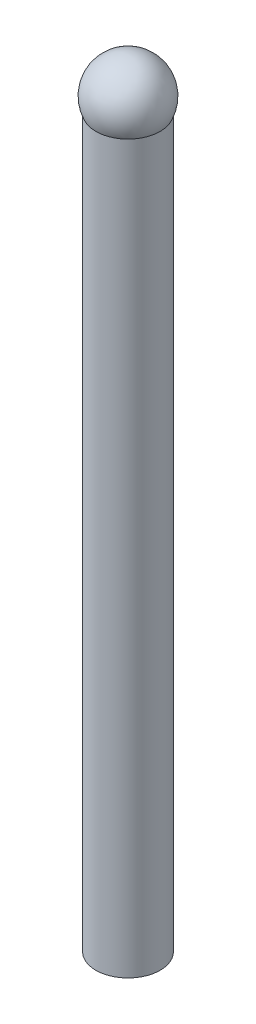
SolidWorks part; units mm, degrees
ref_plane "Спереди" through (0, 0, 0) normal (0, 0, 1) x (1, 0, 0)
ref_plane "Сверху" through (0, 0, 0) normal (0, 1, 0) x (1, 0, 0)
ref_plane "Справа" through (0, 0, 0) normal (1, 0, 0) x (0, 0, -1)
sketch "Эскиз1" plane through (0, 0, 0) normal (0, 1, 0) x (1, 0, 0)
  circle A0 centre (0, 0) radius 0.65
extrude "Бобышка-Вытянуть1" add sketch "Эскиз1" along normal blind 15
sketch "Эскиз3" plane through (0, 0, 0) normal (0, 0, 1) x (1, 0, 0)
  line L0 (0, 0) -> (0, 15.0009) construction
  line L1 (0.7154, 15.0009) -> (0.65, 15) construction
  line L2 (0.65, 15) -> (0.65, 14.702) construction
  line L3 (0.65, 0) -> (0.65, 15) construction
  line L4 (0.65, 14.702) -> (-0.65, 14.702) construction
  line L5 (-0.65, 14.702) -> (-0.65, 15) construction
  line L6 (-0.65, 15) -> (-0.7154, 15.0009) construction
  line L7 (0.7154, 15.0009) -> (-0.7154, 15.0009)
  circle A0 centre (0, 15.0009) radius 0.7154
revolve "Повернуть23" add sketch "Эскиз3" angle 360 about L7 region at (0, 15.3045, 0)
